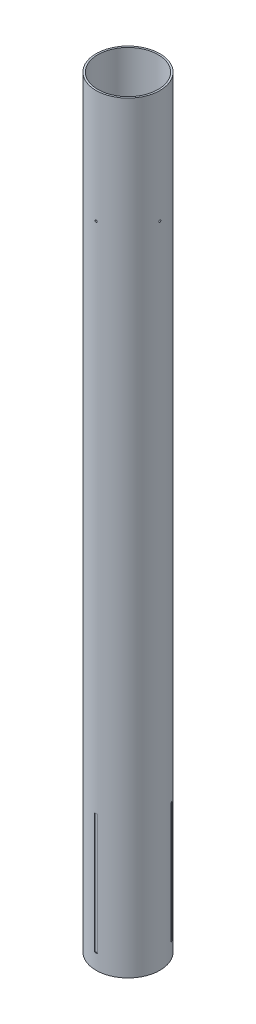
SolidWorks part; units mm, degrees
ref_plane "Front Plane" through (0, 0, 0) normal (0, 0, 1) x (1, 0, 0)
ref_plane "Top Plane" through (0, 0, 0) normal (0, 1, 0) x (1, 0, 0)
ref_plane "Right Plane" through (0, 0, 0) normal (1, 0, 0) x (0, 0, -1)
sketch "Sketch1" plane through (0, 0, 0) normal (0, 1, 0) x (1, 0, 0)
  circle A0 centre (0, 0) radius 53.721
  circle A1 centre (0, 0) radius 50.8
  dimension "D1" = 107.442
  dimension "D2" = 101.6
extrude "Tube Extrusion" add sketch "Sketch1" along normal blind 1282.7
ref_plane "Plane1" through (0, 0, 53.721) normal (0, 0, 1) x (1, 0, 0)
sketch "Sketch2" plane through (0, 0, 53.721) normal (0, 0, 1) x (1, 0, 0)
  line L0 (0, 1282.7) -> (0, 0) construction
  line L3 (53.721, 1282.7) -> (-53.721, 1282.7) construction
  circle A0 centre (0, 1092.2) radius 1.6383
  dimension "D1" = 3.2766
  dimension "D2" = 1092.2
extrude "Engine Block Hole" cut sketch "Sketch2" against normal up to next
pattern_circular "CirPattern1" count 4 over 360 about axis through (0, 1282.7, 0) along (0, -1, 0) of "Engine Block Hole"
sketch "Sketch3" plane through (0, 0, 53.721) normal (0, 0, 1) x (1, 0, 0)
  line L0 (0, 0) -> (0, 25.4) construction
  line L1 (-53.721, 0) -> (53.721, 0) construction
  line L3 (-2.667, 228.6) -> (2.667, 228.6)
  line L4 (-2.667, 228.6) -> (-2.667, 25.4)
  line L5 (-2.667, 25.4) -> (2.667, 25.4)
  line L6 (2.667, 228.6) -> (2.667, 25.4)
  point P8 (0, 25.4)
  dimension "D1" = 25.4
  dimension "D2" = 203.2
  dimension "D3" = 5.334
extrude "Fin Slots" cut sketch "Sketch3" against normal blind 1.27
pattern_circular "CirPattern2" count 3 over 360 about axis through (0, 1282.7, 0) along (0, -1, 0) of "Fin Slots"
